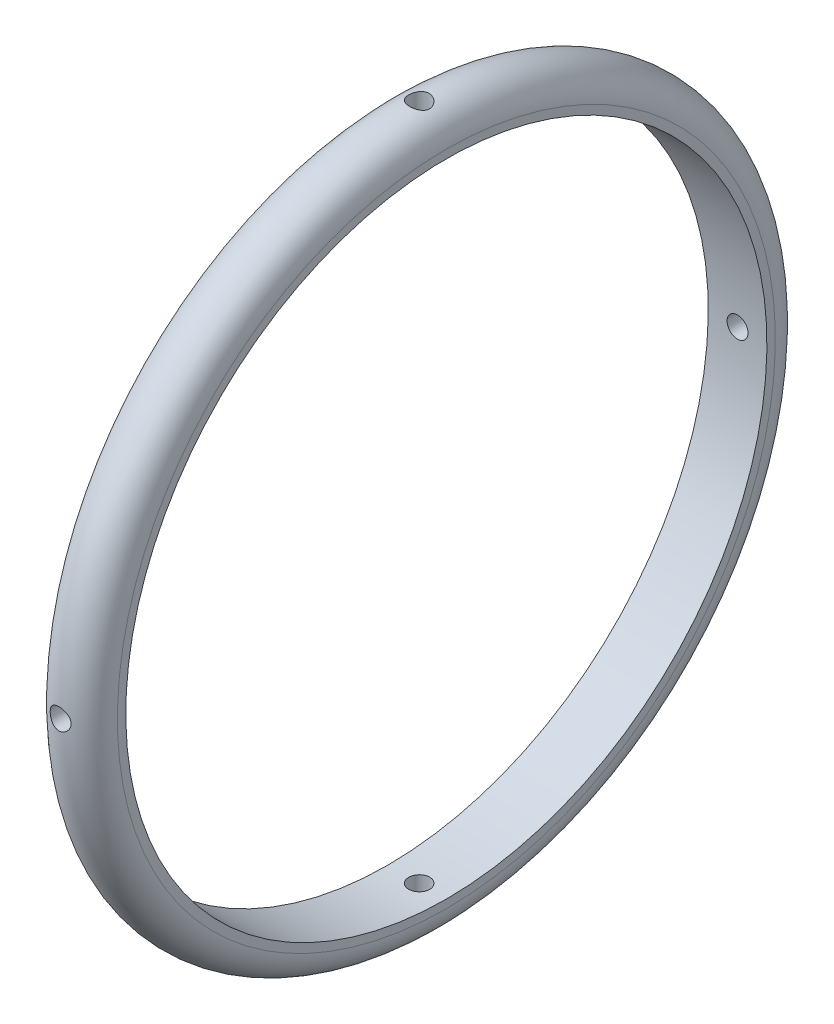
SolidWorks part; units mm, degrees
ref_plane "Front Plane" through (0, 0, 0) normal (0, 0, 1) x (1, 0, 0)
ref_plane "Top Plane" through (0, 0, 0) normal (0, 1, 0) x (1, 0, 0)
ref_plane "Right Plane" through (0, 0, 0) normal (1, 0, 0) x (0, 0, -1)
sketch "Sketch1" plane through (0, 0, 0) normal (0, 0, 1) x (1, 0, 0)
  line L1 (0, 0) -> (14, 0) construction
  line L2 (0, 0) -> (0, 78.5) construction
  line L3 (0, 78.5) -> (14, 78.5)
  line L4 (14, 0) -> (14, 78.5) construction
  line L5 (0, 78.5) -> (14, 78.5)
  line L6 (0, 78.5) -> (0, 76.5)
  line L7 (0, 76.5) -> (14, 76.5)
  line L8 (14, 78.5) -> (14, 76.5)
  arc A0 (0, 78.5) -> (14, 78.5) centre (7, 78.5) cw
  circle A1 centre (7, 0) radius 2.5
  dimension "D4" = 5
  dimension "D1" = 78.5
  dimension "D2" = 14
  dimension "D3" = 2
revolve "Revolve1" add sketch "Sketch1" angle 360 about L1 region at (7, 81.4709, 0) region at (7, 77.5, 0)
extrude "Cut-Extrude1" cut sketch "Sketch1<3>" against normal up to surface and the other way up to surface contours A1 region at (7, 0, 0) up to face at (14, -78.5, 0) other way up to face at (14, -78.5, 0)
sketch "Sketch1<3>" plane through (0, 0, 0) normal (0, 0, 1) x (1, 0, 0) same geometry as "Sketch1"
sketch "Sketch2" plane through (0, 0, 0) normal (0, 1, 0) x (1, 0, 0)
  line L0 (0, 0) -> (15, 0)
  circle A0 centre (7.5, 0) radius 2.5
  dimension "D1" = 5
  dimension "D2" = 15
extrude "Cut-Extrude2" cut sketch "Sketch2" against normal up to surface and the other way up to surface contours L0 A0 | L0 A0 region at (7.5, 0, -1.061) region at (7.5, 0, 1.061) up to face at (8.8446, 1.6874, -85.2359) other way up to face at (8.8446, 1.6874, -85.2359)
